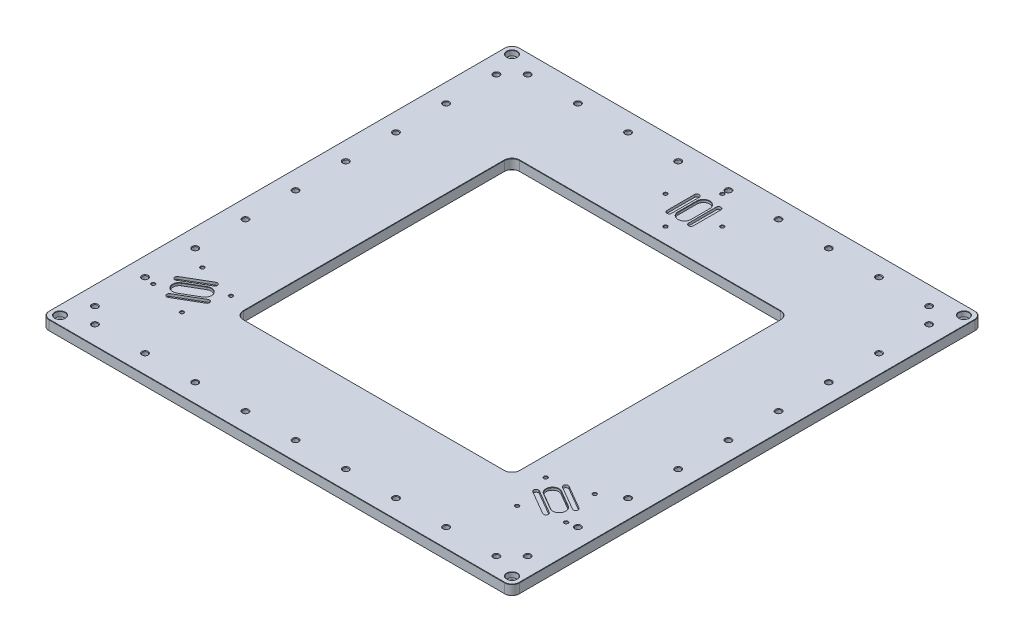
SolidWorks part; units mm, degrees
material "6061-T6 (SS)"
ref_plane "Front Plane" through (0, 0, 0) normal (0, 0, 1) x (1, 0, 0)
ref_plane "Top Plane" through (0, 0, 0) normal (0, 1, 0) x (1, 0, 0)
ref_plane "Right Plane" through (0, 0, 0) normal (1, 0, 0) x (0, 0, -1)
sketch "Sketch1" plane through (0, 0, 0) normal (0, 1, 0) x (1, 0, 0)
  line L1 (-187.5, -187.5) -> (187.5, -187.5)
  line L2 (-187.5, -187.5) -> (-187.5, 187.5)
  line L3 (-187.5, 187.5) -> (187.5, 187.5)
  line L4 (187.5, -187.5) -> (187.5, 187.5)
  line L5 (-187.5, -187.5) -> (187.5, 187.5) construction
  line L6 (-187.5, 187.5) -> (187.5, -187.5) construction
  point P0 (0, 0)
  dimension "D1" = 375
extrude "Boss-Extrude1" add sketch "Sketch1" along normal blind 8
hole_wizard "CBORE for M4 SHCS1" positions "Sketch4" profile "Sketch3" counterbore size "M4" standard "ANSI Metric" end condition up to next
sketch "Sketch4" plane through (0, 8, 0) normal (0, 1, 0) x (1, 0, 0)
  line L0 (0, 0) -> (-180.1218, -180.1218) construction
  line L2 (0, 0) -> (-180.1218, 0) construction
  line L3 (-180.1218, 0) -> (-180.1218, -180.1218) construction
  circle A0 centre (0, 0) radius 254.7307
  point P7 (-180.1218, -180.1218)
  dimension "D1" = 45
  dimension "D2" = 180.1218
sketch "Sketch3" plane through (-180.1218, 8, 180.1218) normal (1, 0, 0) x (0, 0, 1)
  line L0 (0, 0) -> (0, 8)
  line L1 (0, 8) -> (2.15, 8)
  line L3 (2.15, 8) -> (2.15, 4)
  line L4 (2.15, 4) -> (4, 4)
  line L5 (4, 4) -> (4, 0)
  line L7 (4, 0) -> (0, 0)
  line L11 (0, -6.35) -> (0, 107.95) construction
  dimension "Thru Hole Dia." = 4.3
  dimension "Thru Hole Depth" = 8
  dimension "C'Bore Dia." = 8
  dimension "C'Bore Depth" = 4
ref_axis "Axis1" through (0, 10.5, 0) along (0, -1, 0)
hole_wizard "M5x0.8 Tapped Hole1" positions "Sketch15" profile "Sketch16" tap size "M5x0.8" standard "ANSI Metric" end condition up to next
sketch "Sketch15" plane through (0, 8, 0) normal (0, 1, 0) x (1, 0, 0)
  line L1 (172.5, -172.5) -> (-172.5, -172.5)
  line L2 (172.5, -172.5) -> (172.5, 172.5)
  line L3 (172.5, 172.5) -> (-172.5, 172.5)
  line L4 (-172.5, -172.5) -> (-172.5, 172.5)
  line L5 (172.5, -172.5) -> (-172.5, 172.5) construction
  line L6 (172.5, 172.5) -> (-172.5, -172.5) construction
  line L9 (152, -152) -> (-152, -152) construction
  line L10 (152, -152) -> (152, 152) construction
  line L11 (152, 152) -> (-152, 152) construction
  line L12 (-152, -152) -> (-152, 152) construction
  line L13 (152, -152) -> (-152, 152) construction
  line L14 (152, 152) -> (-152, -152) construction
  point P1 (0, 0)
  point P86 (0, 0)
  point P191 (-160, 172.5)
  point P197 (-120, 172.5)
  point P198 (-80, 172.5)
  point P199 (-40, 172.5)
  point P200 (0, 172.5)
  point P201 (40, 172.5)
  point P202 (80, 172.5)
  point P203 (120, 172.5)
  point P204 (160, 172.5)
  dimension "D1" = 345
  dimension "D2" = 304
  dimension "D4" = 40
  dimension "D3" = 9
cosmetic thread "Hole Thread1" parameters "D2"=5
cosmetic thread "Hole Thread2" parameters "D2"=5
cosmetic thread "Hole Thread3" parameters "D2"=5
cosmetic thread "Hole Thread4" parameters "D2"=5
cosmetic thread "Hole Thread5" parameters "D2"=5
cosmetic thread "Hole Thread6" parameters "D2"=5
cosmetic thread "Hole Thread7" parameters "D2"=5
cosmetic thread "Hole Thread8" parameters "D2"=5
cosmetic thread "Hole Thread9" parameters "D2"=5
sketch "Sketch16" plane through (0, 8, 0) normal (1, 0, 0) x (0, 0, 1)
  line L0 (0, 0) -> (0, 8)
  line L1 (0, 8) -> (2.525, 8)
  line L2 (2.1, 7.575) -> (2.1, 0.425)
  line L3 (2.1, 0.425) -> (2.525, 0)
  line L5 (2.525, 0) -> (0, 0)
  line L6 (-2.1, 0.425) -> (-2.525, 0) construction
  line L7 (2.525, 8) -> (2.1, 7.575)
  line L8 (-2.525, 8) -> (-2.1, 7.575) construction
  line L11 (0, -6.35) -> (0, 107.95) construction
  dimension "Thru Tap Drill Dia." = 4.2
  dimension "Thru Tap Drill Depth" = 8
  dimension "Near C'Sink Dia." = 5.05
  dimension "Near C'Sink Angle" = 90
  dimension "Far C'Sink Dia." = 5.05
  dimension "Far C'Sink Angle" = 90
cosmetic thread "Hole Thread52" parameters "D2"=5
pattern_circular "CirPattern1" count 4 over 360 about axis through (0, 10.5, 0) along (0, -1, 0) of "CBORE for M4 SHCS1", "M5x0.8 Tapped Hole1"
cosmetic thread "Hole Thread12" parameters "D2"=5
cosmetic thread "Hole Thread13" parameters "D2"=5
cosmetic thread "Hole Thread14" parameters "D2"=5
cosmetic thread "Hole Thread15" parameters "D2"=5
cosmetic thread "Hole Thread16" parameters "D2"=5
cosmetic thread "Hole Thread17" parameters "D2"=5
cosmetic thread "Hole Thread18" parameters "D2"=5
cosmetic thread "Hole Thread19" parameters "D2"=5
cosmetic thread "Hole Thread20" parameters "D2"=5
cosmetic thread "Hole Thread21" parameters "D2"=5
cosmetic thread "Hole Thread22" parameters "D2"=5
cosmetic thread "Hole Thread23" parameters "D2"=5
cosmetic thread "Hole Thread24" parameters "D2"=5
cosmetic thread "Hole Thread25" parameters "D2"=5
cosmetic thread "Hole Thread26" parameters "D2"=5
cosmetic thread "Hole Thread27" parameters "D2"=5
cosmetic thread "Hole Thread28" parameters "D2"=5
cosmetic thread "Hole Thread29" parameters "D2"=5
cosmetic thread "Hole Thread30" parameters "D2"=5
cosmetic thread "Hole Thread31" parameters "D2"=5
cosmetic thread "Hole Thread32" parameters "D2"=5
cosmetic thread "Hole Thread33" parameters "D2"=5
cosmetic thread "Hole Thread34" parameters "D2"=5
cosmetic thread "Hole Thread35" parameters "D2"=5
cosmetic thread "Hole Thread36" parameters "D2"=5
cosmetic thread "Hole Thread37" parameters "D2"=5
cosmetic thread "Hole Thread38" parameters "D2"=5
sketch "Bed Holes" plane through (0, 8, 0) normal (0, 1, 0) x (1, 0, 0)
  line L0 (145, -110) -> (-145, -110) construction
  line L1 (0, -110) -> (0, 145) construction
  line L2 (152, 152) -> (152, -152) construction
  line L3 (152, 152) -> (-152, 152) construction
  line L4 (-152, 152) -> (-152, -152) construction
  line L5 (-152, -152) -> (152, -152) construction
  point P4 (0, -110)
  point P13 (0, -152)
  point P14 (152, 0)
  dimension "D1" = 255
  dimension "D2" = 7
  dimension "D3" = 304
  dimension "D4" = 7
sketch "Sketch7" plane through (0, 8, 0) normal (0, 1, 0) x (1, 0, 0)
  line L0 (-145, -110) -> (0, 145) construction
  line L1 (0, 145) -> (145, -110) construction
  line L2 (145, -110) -> (-145, -110) construction
  line L3 (-140.6453, -117.4857) -> (-149.3547, -102.5143) construction
  line L4 (-158.8629, -108.0455) -> (-139.8466, -96.983) construction
  line L5 (-159.8259, -106.3901) -> (-140.8096, -95.3276)
  line L8 (-157.8999, -109.7009) -> (-138.8836, -98.6384)
  line L11 (-95.2825, -110) -> (-120.4245, -66.781) construction
  line L12 (-150.1534, -123.017) -> (-131.1371, -111.9545) construction
  line L13 (-151.1164, -121.3616) -> (-132.1001, -110.2991)
  line L14 (0, -110) -> (0, 145) construction
  line L16 (-145, -110) -> (0, -25.6482) construction
  line L17 (0, -25.6482) -> (0, 145) construction
  line L19 (145, -110) -> (0, -25.6482) construction
  line L20 (-149.1904, -124.6724) -> (-130.1741, -113.6099)
  line L21 (0, -25.6482) -> (0, -110) construction
  line L23 (158.8629, -108.0455) -> (139.8466, -96.983) construction
  line L24 (159.8259, -106.3901) -> (140.8096, -95.3276)
  line L25 (157.8999, -109.7009) -> (138.8836, -98.6384)
  line L26 (150.1534, -123.017) -> (131.1371, -111.9545) construction
  line L27 (151.1164, -121.3616) -> (132.1001, -110.2991)
  line L28 (149.1904, -124.6724) -> (130.1741, -113.6099)
  line L29 (8.6603, 145) -> (-8.6603, 145) construction
  line L30 (-8.6603, 156) -> (-8.6603, 134) construction
  line L31 (-6.7451, 156) -> (-6.7451, 134)
  line L32 (-10.5754, 156) -> (-10.5754, 134)
  line L33 (8.6603, 156) -> (8.6603, 134) construction
  line L34 (10.5754, 156) -> (10.5754, 134)
  line L35 (6.7451, 156) -> (6.7451, 134)
  line L36 (145, -110) -> (-145, -110) construction
  arc A0 (-159.8259, -106.3901) -> (-157.8999, -109.7009) centre (-158.8629, -108.0455) ccw
  arc A1 (-138.8836, -98.6384) -> (-140.8096, -95.3276) centre (-139.8466, -96.983) ccw
  arc A2 (-151.1164, -121.3616) -> (-149.1904, -124.6724) centre (-150.1534, -123.017) ccw
  arc A3 (-130.1741, -113.6099) -> (-132.1001, -110.2991) centre (-131.1371, -111.9545) ccw
  arc A4 (159.8259, -106.3901) -> (157.8999, -109.7009) centre (158.8629, -108.0455) cw
  arc A5 (138.8836, -98.6384) -> (140.8096, -95.3276) centre (139.8466, -96.983) cw
  arc A6 (151.1164, -121.3616) -> (149.1904, -124.6724) centre (150.1534, -123.017) cw
  arc A7 (130.1741, -113.6099) -> (132.1001, -110.2991) centre (131.1371, -111.9545) cw
  arc A8 (-6.7451, 156) -> (-10.5754, 156) centre (-8.6603, 156) ccw
  arc A9 (-10.5754, 134) -> (-6.7451, 134) centre (-8.6603, 134) ccw
  arc A10 (10.5754, 156) -> (6.7451, 156) centre (8.6603, 156) ccw
  arc A11 (6.7451, 134) -> (10.5754, 134) centre (8.6603, 134) ccw
  point P5 (-149.3547, -102.5143)
  point P8 (-145, -110)
  point P17 (-140.6453, -117.4857)
  point P25 (149.3547, -102.5143)
  point P33 (140.6453, -117.4857)
  point P41 (0, 145)
  point P43 (-8.6603, 145)
  point P49 (8.6603, 145)
  point P58 (-107.8535, -88.3905)
  dimension "D4" = 22
  dimension "D3" = 1.9151
  dimension "D1" = 50
  dimension "D2" = 17.3205
extrude "Cut-Extrude2" cut sketch "Sketch7" against normal blind 2
sketch "Sketch5" plane through (0, 8, 0) normal (0, 1, 0) x (1, 0, 0)
  line L1 (110, -110) -> (-110, -110)
  line L2 (110, -110) -> (110, 110)
  line L3 (110, 110) -> (-110, 110)
  line L4 (-110, -110) -> (-110, 110)
  line L5 (110, -110) -> (-110, 110) construction
  line L6 (110, 110) -> (-110, -110) construction
  point P0 (0, 0)
  dimension "D1" = 220
extrude "Cut-Extrude3" cut sketch "Sketch5" against normal up to surface (8 mm away) up to face at (-172.5, 0, 162.525)
sketch "Sketch11" plane through (0, 8, 0) normal (0, 1, 0) x (1, 0, 0)
  line L0 (22.6274, 145) -> (0, 122.3726)
  line L1 (-133.622, -129.5587) -> (-164.5587, -121.378)
  line L2 (-133.622, -129.5587) -> (-125.4413, -98.622)
  line L3 (-125.4413, -98.622) -> (-156.378, -90.4413)
  line L4 (-164.5587, -121.378) -> (-156.378, -90.4413)
  line L5 (-133.622, -129.5587) -> (-156.378, -90.4413) construction
  line L6 (-125.4413, -98.622) -> (-164.5587, -121.378) construction
  line L7 (164.5587, -121.378) -> (133.622, -129.5587)
  line L8 (164.5587, -121.378) -> (156.378, -90.4413)
  line L9 (156.378, -90.4413) -> (125.4413, -98.622)
  line L10 (133.622, -129.5587) -> (125.4413, -98.622)
  line L11 (164.5587, -121.378) -> (125.4413, -98.622) construction
  line L12 (156.378, -90.4413) -> (133.622, -129.5587) construction
  line L13 (22.6274, 145) -> (0, 167.6274)
  line L14 (0, 122.3726) -> (-22.6274, 145)
  line L15 (0, 167.6274) -> (-22.6274, 145)
  line L16 (22.6274, 145) -> (-22.6274, 145) construction
  line L17 (0, 122.3726) -> (0, 167.6274) construction
  line L18 (0, -110) -> (0, 145) construction
  line L19 (-132.1001, -110.2991) -> (-151.1164, -121.3616) construction
  line L20 (151.1164, -121.3616) -> (132.1001, -110.2991) construction
  point P0 (-145, -110)
  point P6 (145, -110)
  point P13 (0, 145)
  dimension "D1" = 32
hole_wizard "M3x0.5 Tapped Hole1" positions "Sketch12" profile "Sketch13" tap size "M3x0.5" standard "ANSI Metric" end condition up to next
sketch "Sketch12" plane through (0, 8, 0) normal (0, 1, 0) x (1, 0, 0)
  point P0 (-164.5587, -121.378)
  point P3 (-125.4413, -98.622)
  point P6 (125.4413, -98.622)
  point P9 (164.5587, -121.378)
  point P12 (0, 122.3726)
  point P15 (0, 167.6274)
  point P19 (-156.378, -90.4413)
  point P22 (-133.622, -129.5587)
  point P25 (133.622, -129.5587)
  point P28 (156.378, -90.4413)
  point P31 (22.6274, 145)
  point P34 (-22.6274, 145)
sketch "Sketch13" plane through (-164.5587, 8, 121.378) normal (1, 0, 0) x (0, 0, 1)
  line L0 (0, 0) -> (0, 8)
  line L1 (0, 8) -> (1.25, 8)
  line L2 (1.25, 8) -> (1.25, 0.275)
  line L3 (1.25, 0.275) -> (1.525, 0)
  line L5 (1.525, 0) -> (0, 0)
  line L6 (-1.25, 0.275) -> (-1.525, 0) construction
  line L11 (0, -6.35) -> (0, 107.95) construction
  dimension "Thru Tap Drill Dia." = 2.5
  dimension "Thru Tap Drill Depth" = 8
  dimension "Near C'Sink Dia." = 3.05
  dimension "Near C'Sink Angle" = 90
cosmetic thread "Hole Thread39" parameters "D2"=3
cosmetic thread "Hole Thread40" parameters "D2"=3
cosmetic thread "Hole Thread41" parameters "D2"=3
cosmetic thread "Hole Thread42" parameters "D2"=3
cosmetic thread "Hole Thread43" parameters "D2"=3
cosmetic thread "Hole Thread44" parameters "D2"=3
cosmetic thread "Hole Thread45" parameters "D2"=3
cosmetic thread "Hole Thread46" parameters "D2"=3
cosmetic thread "Hole Thread47" parameters "D2"=3
cosmetic thread "Hole Thread48" parameters "D2"=3
cosmetic thread "Hole Thread49" parameters "D2"=3
cosmetic thread "Hole Thread50" parameters "D2"=3
sketch "Sketch14" plane through (0, 8, 0) normal (0, 1, 0) x (1, 0, 0)
  line L0 (-151.4828, -113.7713) -> (-138.5172, -106.2287) construction
  line L1 (-153.997, -109.4494) -> (-141.0314, -101.9068)
  line L2 (-148.9686, -118.0932) -> (-136.003, -110.5506)
  line L3 (151.4828, -113.7713) -> (138.5172, -106.2287) construction
  line L4 (148.9686, -118.0932) -> (136.003, -110.5506)
  line L5 (153.997, -109.4494) -> (141.0314, -101.9068)
  line L6 (0, 137.5) -> (0, 152.5) construction
  line L7 (-5, 137.5) -> (-5, 152.5)
  line L8 (5, 137.5) -> (5, 152.5)
  line L9 (-157.8999, -109.7009) -> (-138.8836, -98.6384) construction
  line L10 (138.8836, -98.6384) -> (157.8999, -109.7009) construction
  arc A3 (-153.997, -109.4494) -> (-148.9686, -118.0932) centre (-151.4828, -113.7713) ccw
  arc A4 (-136.003, -110.5506) -> (-141.0314, -101.9068) centre (-138.5172, -106.2287) ccw
  arc A5 (148.9686, -118.0932) -> (153.997, -109.4494) centre (151.4828, -113.7713) ccw
  arc A6 (141.0314, -101.9068) -> (136.003, -110.5506) centre (138.5172, -106.2287) ccw
  arc A7 (-5, 137.5) -> (5, 137.5) centre (0, 137.5) ccw
  arc A8 (5, 152.5) -> (-5, 152.5) centre (0, 152.5) ccw
  point P3 (-145, -110)
  point P12 (145, -110)
  point P20 (0, 145)
  dimension "D1" = 5
  dimension "D2" = 15
extrude "Cut-Extrude4" cut sketch "Sketch14" against normal blind 2
fillet "Fillet2" radius 6 8 edges at (-110, 4, 110) (110, 4, -110) (110, 4, 110) (-110, 4, -110) (187.5, 4, 187.5) (-187.5, 4, 187.5) (187.5, 4, -187.5) (-187.5, 4, -187.5)
chamfer "Chamfer1" distance 0.25 angle 45 48 edges at (0, 8, -132.5) (5, 8, -145) (-5, 8, -145) (0, 8, -157.5) (155.8047, 8, 116.2855) (147.5142, 8, 105.6781) (142.4858, 8, 114.3219) (134.1953, 8, 103.7145) (-134.1953, 8, 103.7145) (-147.5142, 8, 105.6781) (-142.4858, 8, 114.3219) (-155.8047, 8, 116.2855) (110, 0, 0) (108.2426, 0, -108.2426) (108.2426, 0, 108.2426) (0, 0, -110) (0, 0, 110) (-108.2426, 0, -108.2426) (-108.2426, 0, 108.2426) (-110, 0, 0) (110, 8, 0) (108.2426, 8, -108.2426) (108.2426, 8, 108.2426) (0, 8, -110) (0, 8, 110) (-108.2426, 8, -108.2426) (-108.2426, 8, 108.2426) (-110, 8, 0) (0, 0, -187.5) (-185.7426, 0, -185.7426) (185.7426, 0, -185.7426) (-187.5, 0, 0) (187.5, 0, 0) (-185.7426, 0, 185.7426) (185.7426, 0, 185.7426) (0, 0, 187.5) (0, 8, -187.5) (-185.7426, 8, -185.7426) (185.7426, 8, -185.7426) (-187.5, 8, 0) (187.5, 8, 0) (-185.7426, 8, 185.7426) (185.7426, 8, 185.7426) (0, 8, 187.5) (-180.1218, 8, -176.1218) (180.1218, 8, -176.1218) (180.1218, 8, 184.1218) (-180.1218, 8, 184.1218)
